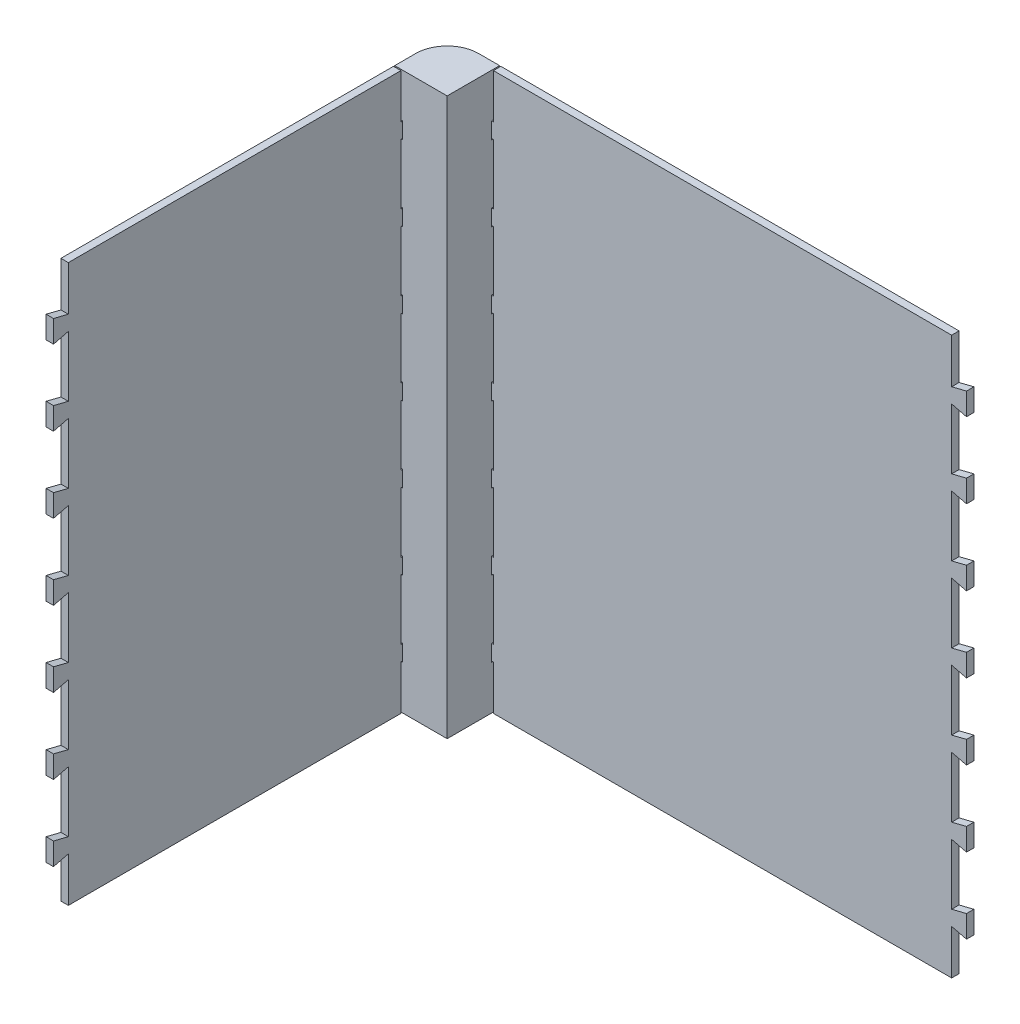
SolidWorks part; units mm, degrees
ref_plane "Front Plane" through (0, 0, 0) normal (0, 0, 1) x (1, 0, 0)
ref_plane "Top Plane" through (0, 0, 0) normal (0, 1, 0) x (1, 0, 0)
ref_plane "Right Plane" through (0, 0, 0) normal (1, 0, 0) x (0, 0, -1)
sketch "Constraints long side" plane through (0, 0, 0) normal (0, 0, 1) x (1, 0, 0)
  line L0 (-101.6, 112.5) -> (-101.6, -112.5) construction
  line L1 (-114.3, 112.5) -> (114.3, 112.5) construction
  line L2 (-114.3, 112.5) -> (-114.3, -112.5) construction
  line L3 (-114.3, -112.5) -> (114.3, -112.5) construction
  line L4 (114.3, 112.5) -> (114.3, -112.5) construction
  line L5 (101.6, 112.5) -> (101.6, -112.5) construction
  line L6 (-101.6, 0) -> (-114.3, 0) construction
  line L7 (114.3, 0) -> (101.6, 0) construction
  line L8 (-92.6, -112.5) -> (-92.6, 112.5) construction
  line L9 (92.6, -112.5) -> (92.6, 112.5) construction
  line L10 (-92.6, 0) -> (-101.6, 0) construction
  line L11 (101.6, 0) -> (92.6, 0) construction
  point P4 (0, 112.5)
  point P6 (-114.3, 0)
  point P20 (0, 0)
  dimension "D1" = 228.6
  dimension "D2" = 225
  dimension "D3" = 12.7
  dimension "D4" = 9
sketch "Constraints short side" plane through (0, 0, 0) normal (1, 0, 0) x (0, 0, -1)
  line L0 (0, 112.5) -> (0, -112.5) construction
  line L1 (0, 112.5) -> (0, -112.5) construction
  line L2 (-76.2, 112.5) -> (-76.2, -112.5) construction
  line L3 (-88.9, 112.5) -> (88.9, 112.5) construction
  line L4 (-88.9, 112.5) -> (-88.9, -112.5) construction
  line L5 (-88.9, -112.5) -> (88.9, -112.5) construction
  line L6 (88.9, 112.5) -> (88.9, -112.5) construction
  line L7 (76.2, 112.5) -> (76.2, -112.5) construction
  line L8 (-76.2, 0) -> (-88.9, 0) construction
  line L9 (76.2, 0) -> (88.9, 0) construction
  line L10 (-67.2, 112.5) -> (-67.2, -112.5) construction
  line L11 (-67.2, 0) -> (-76.2, 0) construction
  line L12 (67.2, 112.5) -> (67.2, -112.5) construction
  line L13 (76.2, 0) -> (67.2, 0) construction
  point P6 (0, 112.5)
  point P7 (0, -112.5)
  point P21 (0, 0)
  point P23 (0, 0)
  dimension "D1" = 177.8
  dimension "D2" = 12.7
  dimension "D3" = 9
sketch "Sketch3" plane through (0, 0, 0) normal (0, 0, 1) x (1, 0, 0)
  line L0 (-98.6, 4.5) -> (-98.6, -4.5)
  line L1 (-98.6, -4.5) -> (-92.6, -3)
  line L2 (-92.6, -112.5) -> (-92.6, 112.5) construction
  line L3 (-98.6, 4.5) -> (-92.6, 3)
  line L4 (-92.6, 3) -> (-92.6, -3)
  line L5 (-92.6, 0) -> (-101.6, 0) construction
  line L6 (-101.6, 112.5) -> (-101.6, -112.5) construction
  line L7 (-98.6, -25.98) -> (-92.6, -27.48)
  line L8 (-92.6, 112.5) -> (92.6, 112.5)
  line L9 (-92.6, 112.5) -> (-92.6, -112.5)
  line L10 (-92.6, -112.5) -> (92.6, -112.5)
  line L11 (92.6, 112.5) -> (92.6, -112.5)
  line L12 (-98.6, -25.98) -> (-98.6, -34.98)
  line L13 (-98.6, -34.98) -> (-92.6, -33.48)
  line L14 (-98.6, -56.46) -> (-92.6, -57.96)
  line L15 (-98.6, -56.46) -> (-98.6, -65.46)
  line L16 (-98.6, -65.46) -> (-92.6, -63.96)
  line L17 (-98.6, -86.94) -> (-92.6, -88.44)
  line L18 (-98.6, -86.94) -> (-98.6, -95.94)
  line L19 (-98.6, -95.94) -> (-92.6, -94.44)
  line L20 (-98.6, -30.48) -> (-92.6, -30.48) construction
  line L21 (-98.6, 0) -> (-92.6, 0) construction
  line L22 (-98.6, 95.94) -> (-92.6, 94.44)
  line L23 (-98.6, 86.94) -> (-92.6, 88.44)
  line L24 (-98.6, 86.94) -> (-98.6, 95.94)
  line L25 (-98.6, 65.46) -> (-92.6, 63.96)
  line L26 (-98.6, 56.46) -> (-98.6, 65.46)
  line L27 (-98.6, 56.46) -> (-92.6, 57.96)
  line L28 (-98.6, 25.98) -> (-92.6, 27.48)
  line L29 (-98.6, 25.98) -> (-98.6, 34.98)
  line L30 (-98.6, 34.98) -> (-92.6, 33.48)
  line L31 (0, 112.5) -> (0, -112.5) construction
  line L32 (98.6, 86.94) -> (92.6, 88.44)
  line L33 (98.6, 86.94) -> (98.6, 95.94)
  line L34 (98.6, 95.94) -> (92.6, 94.44)
  line L35 (98.6, 65.46) -> (92.6, 63.96)
  line L36 (98.6, 56.46) -> (98.6, 65.46)
  line L37 (98.6, 56.46) -> (92.6, 57.96)
  line L38 (98.6, 34.98) -> (92.6, 33.48)
  line L39 (98.6, 25.98) -> (98.6, 34.98)
  line L40 (98.6, 25.98) -> (92.6, 27.48)
  line L41 (98.6, -4.5) -> (92.6, -3)
  line L42 (98.6, 4.5) -> (98.6, -4.5)
  line L43 (98.6, 4.5) -> (92.6, 3)
  line L44 (98.6, -25.98) -> (92.6, -27.48)
  line L45 (98.6, -25.98) -> (98.6, -34.98)
  line L46 (98.6, -34.98) -> (92.6, -33.48)
  line L47 (98.6, -56.46) -> (92.6, -57.96)
  line L48 (98.6, -56.46) -> (98.6, -65.46)
  line L49 (98.6, -65.46) -> (92.6, -63.96)
  line L50 (98.6, -86.94) -> (92.6, -88.44)
  line L51 (98.6, -86.94) -> (98.6, -95.94)
  line L52 (98.6, -95.94) -> (92.6, -94.44)
  point P3 (-98.6, 0)
  point P9 (-92.6, 0)
  dimension "D1" = 6
  dimension "D2" = 9
  dimension "D3" = 3
  dimension "D5" = 30.48
  dimension "D4" = 4
sketch "Sketch4" plane through (0, 0, 0) normal (1, 0, 0) x (0, 0, -1)
  line L0 (-67.2, 3) -> (-73.2, 4.5)
  line L1 (-67.2, 112.5) -> (67.2, 112.5)
  line L2 (-67.2, 112.5) -> (-67.2, -112.5)
  line L3 (-67.2, -112.5) -> (67.2, -112.5)
  line L4 (67.2, 112.5) -> (67.2, -112.5)
  line L5 (-73.2, 4.5) -> (-73.2, -4.5)
  line L6 (-73.2, -4.5) -> (-67.2, -3)
  line L7 (-67.2, 0) -> (-76.2, 0) construction
  line L8 (-67.2, 3) -> (-67.2, -3) construction
  line L9 (-76.2, 112.5) -> (-76.2, -112.5) construction
  line L10 (-73.2, -34.98) -> (-67.2, -33.48)
  line L11 (-73.2, -25.98) -> (-73.2, -34.98)
  line L12 (-67.2, -27.48) -> (-73.2, -25.98)
  line L13 (-73.2, -65.46) -> (-67.2, -63.96)
  line L14 (-73.2, -56.46) -> (-73.2, -65.46)
  line L15 (-67.2, -57.96) -> (-73.2, -56.46)
  line L16 (-73.2, -95.94) -> (-67.2, -94.44)
  line L17 (-73.2, -86.94) -> (-73.2, -95.94)
  line L18 (-67.2, -88.44) -> (-73.2, -86.94)
  line L19 (-73.2, -30.48) -> (-67.2, -30.48) construction
  line L20 (-73.2, 0) -> (-67.2, 0) construction
  line L21 (-73.2, 95.94) -> (-67.2, 94.44)
  line L22 (-73.2, 86.94) -> (-73.2, 95.94)
  line L23 (-67.2, 88.44) -> (-73.2, 86.94)
  line L24 (-73.2, 65.46) -> (-67.2, 63.96)
  line L25 (-73.2, 56.46) -> (-73.2, 65.46)
  line L26 (-67.2, 57.96) -> (-73.2, 56.46)
  line L27 (-73.2, 34.98) -> (-67.2, 33.48)
  line L28 (-73.2, 25.98) -> (-73.2, 34.98)
  line L29 (-67.2, 27.48) -> (-73.2, 25.98)
  line L30 (-73.2, 4.5) -> (-67.2, 3)
  line L31 (-67.2, -3) -> (-73.2, -4.5)
  line L32 (0, 112.5) -> (0, -112.5) construction
  line L33 (73.2, 0) -> (67.2, 0) construction
  line L34 (73.2, -30.48) -> (67.2, -30.48) construction
  line L35 (67.2, -3) -> (73.2, -4.5)
  line L36 (73.2, 4.5) -> (67.2, 3)
  line L37 (67.2, 27.48) -> (73.2, 25.98)
  line L38 (73.2, 25.98) -> (73.2, 34.98)
  line L39 (73.2, 34.98) -> (67.2, 33.48)
  line L40 (67.2, 57.96) -> (73.2, 56.46)
  line L41 (73.2, 56.46) -> (73.2, 65.46)
  line L42 (73.2, 65.46) -> (67.2, 63.96)
  line L43 (67.2, 88.44) -> (73.2, 86.94)
  line L44 (73.2, 86.94) -> (73.2, 95.94)
  line L45 (73.2, 95.94) -> (67.2, 94.44)
  line L46 (67.2, -88.44) -> (73.2, -86.94)
  line L47 (73.2, -86.94) -> (73.2, -95.94)
  line L48 (73.2, -95.94) -> (67.2, -94.44)
  line L49 (67.2, -57.96) -> (73.2, -56.46)
  line L50 (73.2, -56.46) -> (73.2, -65.46)
  line L51 (73.2, -65.46) -> (67.2, -63.96)
  line L52 (67.2, -27.48) -> (73.2, -25.98)
  line L53 (73.2, -25.98) -> (73.2, -34.98)
  line L54 (73.2, -34.98) -> (67.2, -33.48)
  line L55 (73.2, -4.5) -> (67.2, -3)
  line L56 (73.2, 4.5) -> (73.2, -4.5)
  line L57 (67.2, 3) -> (73.2, 4.5)
  point P8 (-73.2, 0)
  point P15 (-67.2, 0)
  point P16 (-67.2, 0)
  dimension "D1" = 9
  dimension "D2" = 6
  dimension "D3" = 3
  dimension "D5" = 30.48
  dimension "D4" = 4
ref_plane "Plane5" through (-114.3, 0, 0) normal (1, 0, 0) x (0, 0, -1)
sketch "Sketch6" plane through (-114.3, 0, 0) normal (1, 0, 0) x (0, 0, -1)
  line L0 (-73.2, 4.5) -> (-73.2, -4.5) construction
  line L1 (-73.2, -95.94) -> (-67.2, -94.44) construction
  line L2 (-73.2, -86.94) -> (-73.2, -95.94) construction
  line L3 (-67.2, -88.44) -> (-73.2, -86.94) construction
  line L4 (-73.2, -65.46) -> (-67.2, -63.96) construction
  line L5 (-73.2, -56.46) -> (-73.2, -65.46) construction
  line L6 (-67.2, -57.96) -> (-73.2, -56.46) construction
  line L7 (-73.2, -34.98) -> (-67.2, -33.48) construction
  line L8 (-73.2, -25.98) -> (-73.2, -34.98) construction
  line L9 (-67.2, -27.48) -> (-73.2, -25.98) construction
  line L10 (-73.2, 34.98) -> (-67.2, 33.48) construction
  line L11 (-73.2, 25.98) -> (-73.2, 34.98) construction
  line L12 (-67.2, 27.48) -> (-73.2, 25.98) construction
  line L13 (-73.2, 65.46) -> (-67.2, 63.96) construction
  line L14 (-73.2, 56.46) -> (-73.2, 65.46) construction
  line L15 (-67.2, 57.96) -> (-73.2, 56.46) construction
  line L16 (-73.2, 95.94) -> (-67.2, 94.44) construction
  line L17 (-73.2, 86.94) -> (-73.2, 95.94) construction
  line L18 (-67.2, 88.44) -> (-73.2, 86.94) construction
  line L19 (67.2, 57.96) -> (73.2, 56.46) construction
  line L20 (73.2, 56.46) -> (73.2, 65.46) construction
  line L21 (73.2, 65.46) -> (67.2, 63.96) construction
  line L22 (67.2, 27.48) -> (73.2, 25.98) construction
  line L23 (73.2, 25.98) -> (73.2, 34.98) construction
  line L24 (73.2, 34.98) -> (67.2, 33.48) construction
  line L25 (73.2, 4.5) -> (73.2, -4.5) construction
  line L26 (67.2, -27.48) -> (73.2, -25.98) construction
  line L27 (73.2, -25.98) -> (73.2, -34.98) construction
  line L28 (73.2, -34.98) -> (67.2, -33.48) construction
  line L29 (67.2, -57.96) -> (73.2, -56.46) construction
  line L30 (73.2, -56.46) -> (73.2, -65.46) construction
  line L31 (73.2, -65.46) -> (67.2, -63.96) construction
  line L32 (67.2, -88.44) -> (73.2, -86.94) construction
  line L33 (73.2, -86.94) -> (73.2, -95.94) construction
  line L34 (73.2, -95.94) -> (67.2, -94.44) construction
  line L35 (67.2, 88.44) -> (73.2, 86.94) construction
  line L36 (73.2, 86.94) -> (73.2, 95.94) construction
  line L37 (73.2, 95.94) -> (67.2, 94.44) construction
  line L38 (-73.2, -4.5) -> (-67.2, -3) construction
  line L39 (-67.2, -3) -> (-73.2, -4.5) construction
  line L40 (-67.2, 112.5) -> (67.2, 112.5) construction
  line L41 (67.2, 112.5) -> (67.2, -112.5) construction
  line L42 (-67.2, -112.5) -> (67.2, -112.5) construction
  line L43 (-67.2, 112.5) -> (-67.2, -112.5) construction
  line L44 (-67.2, 3) -> (-73.2, 4.5) construction
  line L45 (-73.2, 4.5) -> (-67.2, 3) construction
  line L46 (73.2, 4.5) -> (67.2, 3) construction
  line L47 (67.2, 3) -> (73.2, 4.5) construction
  line L48 (67.2, -3) -> (73.2, -4.5) construction
  line L49 (73.2, -4.5) -> (67.2, -3) construction
  line L50 (-73.2, 4.5) -> (-73.2, -4.5)
  line L51 (-73.2, -95.94) -> (-67.2, -94.44)
  line L52 (-73.2, -86.94) -> (-73.2, -95.94)
  line L53 (-67.2, -88.44) -> (-73.2, -86.94)
  line L54 (-73.2, -65.46) -> (-67.2, -63.96)
  line L55 (-73.2, -56.46) -> (-73.2, -65.46)
  line L56 (-67.2, -57.96) -> (-73.2, -56.46)
  line L57 (-73.2, -34.98) -> (-67.2, -33.48)
  line L58 (-73.2, -25.98) -> (-73.2, -34.98)
  line L59 (-67.2, -27.48) -> (-73.2, -25.98)
  line L60 (-73.2, 34.98) -> (-67.2, 33.48)
  line L61 (-73.2, 25.98) -> (-73.2, 34.98)
  line L62 (-67.2, 27.48) -> (-73.2, 25.98)
  line L63 (-73.2, 65.46) -> (-67.2, 63.96)
  line L64 (-73.2, 56.46) -> (-73.2, 65.46)
  line L65 (-67.2, 57.96) -> (-73.2, 56.46)
  line L66 (-73.2, 95.94) -> (-67.2, 94.44)
  line L67 (-73.2, 86.94) -> (-73.2, 95.94)
  line L68 (-67.2, 88.44) -> (-73.2, 86.94)
  line L69 (67.2, 57.96) -> (73.2, 56.46)
  line L70 (73.2, 56.46) -> (73.2, 65.46)
  line L71 (73.2, 65.46) -> (67.2, 63.96)
  line L72 (67.2, 27.48) -> (73.2, 25.98)
  line L73 (73.2, 25.98) -> (73.2, 34.98)
  line L74 (73.2, 34.98) -> (67.2, 33.48)
  line L75 (73.2, 4.5) -> (73.2, -4.5)
  line L76 (67.2, -27.48) -> (73.2, -25.98)
  line L77 (73.2, -25.98) -> (73.2, -34.98)
  line L78 (73.2, -34.98) -> (67.2, -33.48)
  line L79 (67.2, -57.96) -> (73.2, -56.46)
  line L80 (73.2, -56.46) -> (73.2, -65.46)
  line L81 (73.2, -65.46) -> (67.2, -63.96)
  line L82 (67.2, -88.44) -> (73.2, -86.94)
  line L83 (73.2, -86.94) -> (73.2, -95.94)
  line L84 (73.2, -95.94) -> (67.2, -94.44)
  line L85 (67.2, 88.44) -> (73.2, 86.94)
  line L86 (73.2, 86.94) -> (73.2, 95.94)
  line L87 (73.2, 95.94) -> (67.2, 94.44)
  line L88 (-73.2, -4.5) -> (-67.2, -3)
  line L89 (-67.2, -3) -> (-73.2, -4.5)
  line L90 (-67.2, 112.5) -> (67.2, 112.5)
  line L91 (67.2, 112.5) -> (67.2, -112.5)
  line L92 (-67.2, -112.5) -> (67.2, -112.5)
  line L93 (-67.2, 112.5) -> (-67.2, -112.5)
  line L94 (-67.2, 3) -> (-73.2, 4.5)
  line L95 (-73.2, 4.5) -> (-67.2, 3)
  line L96 (73.2, 4.5) -> (67.2, 3)
  line L97 (67.2, 3) -> (73.2, 4.5)
  line L98 (67.2, -3) -> (73.2, -4.5)
  line L99 (73.2, -4.5) -> (67.2, -3)
extrude "Boss-Extrude1" add sketch "Sketch6" along normal blind 3 contours L82 L91 L84 L83 | L79 L91 L81 L80 | L76 L91 L78 L77 | L90 L93 L92 L91 | L91 L98 L75 L96 | L74 L91 L72 L73 | L71 L91 L69 L70 | L87 L91 L85 L86 | L93 L53 L52 L51 | L93 L56 L55 L54 | L93 L59 L58 L57 | L93 L94 L50 L88 | L93 L60 L61 L62 | L93 L63 L64 L65 | L93 L66 L67 L68 region at (-114.3, 0, 70.4) region at (-114.3, 0, 0) region at (-114.3, 30.48, 70.4) region at (-114.3, -30.48, 70.4) region at (-114.3, 60.96, 70.4) region at (-114.3, -60.96, 70.4) region at (-114.3, 91.44, 70.4) region at (-114.3, -91.44, 70.4) region at (-114.3, 91.44, -70.4) region at (-114.3, -91.44, -70.4) region at (-114.3, 60.96, -70.4) region at (-114.3, -60.96, -70.4) region at (-114.3, 30.48, -70.4) region at (-114.3, -30.48, -70.4) region at (-114.3, 0, -70.4)
ref_plane "Plane6" through (0, 0, -88.9) normal (0, 0, 1) x (1, 0, 0)
sketch "Sketch7" plane through (0, 0, -88.9) normal (0, 0, 1) x (1, 0, 0)
  line L0 (-98.6, -86.94) -> (-92.6, -88.44) construction
  line L1 (-98.6, -86.94) -> (-98.6, -95.94) construction
  line L2 (-98.6, -95.94) -> (-92.6, -94.44) construction
  line L3 (-98.6, -56.46) -> (-92.6, -57.96) construction
  line L4 (92.6, 112.5) -> (-92.6, 112.5)
  line L5 (92.6, -112.5) -> (92.6, 112.5)
  line L6 (-92.6, -112.5) -> (92.6, -112.5)
  line L7 (-92.6, 112.5) -> (-92.6, -112.5)
  line L8 (92.6, 112.5) -> (-92.6, 112.5)
  line L9 (92.6, -112.5) -> (92.6, 112.5)
  line L10 (-92.6, -112.5) -> (92.6, -112.5)
  line L11 (-92.6, 112.5) -> (-92.6, -112.5)
  line L12 (-98.6, 4.5) -> (-98.6, -4.5)
  line L13 (-98.6, -4.5) -> (-92.6, -3)
  line L14 (-92.6, -3) -> (-92.6, 3)
  line L15 (-92.6, 3) -> (-98.6, 4.5)
  line L16 (-98.6, 4.5) -> (-98.6, -4.5)
  line L17 (-98.6, -4.5) -> (-92.6, -3)
  line L18 (-92.6, -3) -> (-92.6, 3)
  line L19 (-92.6, 3) -> (-98.6, 4.5)
  line L20 (-98.6, -56.46) -> (-98.6, -65.46) construction
  line L21 (-98.6, -65.46) -> (-92.6, -63.96) construction
  line L22 (-98.6, -25.98) -> (-92.6, -27.48) construction
  line L23 (-98.6, -25.98) -> (-98.6, -34.98) construction
  line L24 (-98.6, -34.98) -> (-92.6, -33.48) construction
  line L25 (-98.6, 25.98) -> (-92.6, 27.48) construction
  line L26 (-98.6, 25.98) -> (-98.6, 34.98) construction
  line L27 (-98.6, 34.98) -> (-92.6, 33.48) construction
  line L28 (-98.6, 65.46) -> (-92.6, 63.96) construction
  line L29 (-98.6, 56.46) -> (-98.6, 65.46) construction
  line L30 (-98.6, 56.46) -> (-92.6, 57.96) construction
  line L31 (-98.6, 95.94) -> (-92.6, 94.44) construction
  line L32 (-98.6, 86.94) -> (-98.6, 95.94) construction
  line L33 (-98.6, 86.94) -> (-92.6, 88.44) construction
  line L34 (98.6, -4.5) -> (92.6, -3) construction
  line L35 (98.6, 4.5) -> (98.6, -4.5) construction
  line L36 (98.6, 4.5) -> (92.6, 3) construction
  line L37 (98.6, 34.98) -> (92.6, 33.48) construction
  line L38 (98.6, 25.98) -> (98.6, 34.98) construction
  line L39 (98.6, 25.98) -> (92.6, 27.48) construction
  line L40 (98.6, 65.46) -> (92.6, 63.96) construction
  line L41 (98.6, 56.46) -> (98.6, 65.46) construction
  line L42 (98.6, 56.46) -> (92.6, 57.96) construction
  line L43 (98.6, 86.94) -> (92.6, 88.44) construction
  line L44 (98.6, 86.94) -> (98.6, 95.94) construction
  line L45 (98.6, 95.94) -> (92.6, 94.44) construction
  line L46 (98.6, -86.94) -> (92.6, -88.44) construction
  line L47 (98.6, -86.94) -> (98.6, -95.94) construction
  line L48 (98.6, -95.94) -> (92.6, -94.44) construction
  line L49 (98.6, -56.46) -> (92.6, -57.96) construction
  line L50 (98.6, -56.46) -> (98.6, -65.46) construction
  line L51 (98.6, -65.46) -> (92.6, -63.96) construction
  line L52 (98.6, -25.98) -> (92.6, -27.48) construction
  line L53 (98.6, -25.98) -> (98.6, -34.98) construction
  line L54 (98.6, -34.98) -> (92.6, -33.48) construction
  line L55 (-98.6, -86.94) -> (-92.6, -88.44)
  line L56 (-98.6, -86.94) -> (-98.6, -95.94)
  line L57 (-98.6, -95.94) -> (-92.6, -94.44)
  line L58 (-98.6, -56.46) -> (-92.6, -57.96)
  line L59 (-98.6, -56.46) -> (-98.6, -65.46)
  line L60 (-98.6, -65.46) -> (-92.6, -63.96)
  line L61 (-98.6, -25.98) -> (-92.6, -27.48)
  line L62 (-98.6, -25.98) -> (-98.6, -34.98)
  line L63 (-98.6, -34.98) -> (-92.6, -33.48)
  line L64 (-98.6, 25.98) -> (-92.6, 27.48)
  line L65 (-98.6, 25.98) -> (-98.6, 34.98)
  line L66 (-98.6, 34.98) -> (-92.6, 33.48)
  line L67 (-98.6, 65.46) -> (-92.6, 63.96)
  line L68 (-98.6, 56.46) -> (-98.6, 65.46)
  line L69 (-98.6, 56.46) -> (-92.6, 57.96)
  line L70 (-98.6, 95.94) -> (-92.6, 94.44)
  line L71 (-98.6, 86.94) -> (-98.6, 95.94)
  line L72 (-98.6, 86.94) -> (-92.6, 88.44)
  line L73 (98.6, -4.5) -> (92.6, -3)
  line L74 (98.6, 4.5) -> (98.6, -4.5)
  line L75 (98.6, 4.5) -> (92.6, 3)
  line L76 (98.6, 34.98) -> (92.6, 33.48)
  line L77 (98.6, 25.98) -> (98.6, 34.98)
  line L78 (98.6, 25.98) -> (92.6, 27.48)
  line L79 (98.6, 65.46) -> (92.6, 63.96)
  line L80 (98.6, 56.46) -> (98.6, 65.46)
  line L81 (98.6, 56.46) -> (92.6, 57.96)
  line L82 (98.6, 86.94) -> (92.6, 88.44)
  line L83 (98.6, 86.94) -> (98.6, 95.94)
  line L84 (98.6, 95.94) -> (92.6, 94.44)
  line L85 (98.6, -86.94) -> (92.6, -88.44)
  line L86 (98.6, -86.94) -> (98.6, -95.94)
  line L87 (98.6, -95.94) -> (92.6, -94.44)
  line L88 (98.6, -56.46) -> (92.6, -57.96)
  line L89 (98.6, -56.46) -> (98.6, -65.46)
  line L90 (98.6, -65.46) -> (92.6, -63.96)
  line L91 (98.6, -25.98) -> (92.6, -27.48)
  line L92 (98.6, -25.98) -> (98.6, -34.98)
  line L93 (98.6, -34.98) -> (92.6, -33.48)
  dimension "D1" = 0
  dimension "D2" = 0
extrude "Boss-Extrude2" add sketch "Sketch7" along normal blind 3 separate body contours L8 L11 L10 L9 | L87 L86 L85 L9 | L90 L89 L88 L9 | L93 L92 L91 L9 | L74 L75 L9 L73 | L78 L77 L76 L9 | L81 L80 L79 L9 | L83 L84 L9 L82 | L56 L57 L11 L55 | L59 L60 L11 L58 | L62 L63 L11 L61 | L11 L19 L16 L17 | L66 L65 L64 L11 | L68 L69 L11 L67 | L71 L72 L11 L70 region at (0, 0, -88.9) region at (95.8, 91.44, -88.9) region at (-95.8, 91.44, -88.9) region at (95.8, 60.96, -88.9) region at (-95.8, 60.96, -88.9) region at (95.8, 30.48, -88.9) region at (-95.8, 30.48, -88.9) region at (95.8, 0, -88.9) region at (-95.8, 0, -88.9) region at (95.8, -30.48, -88.9) region at (-95.8, -30.48, -88.9) region at (95.8, -60.96, -88.9) region at (-95.8, -60.96, -88.9) region at (95.8, -91.44, -88.9) region at (-95.8, -91.44, -88.9)
sketch "Sketch8" plane through (0, 0, 0) normal (0, 1, 0) x (1, 0, 0)
  line L0 (-101.6, 0) -> (-101.6, 88.9) construction
  line L2 (-92.6, 0) -> (-101.6, 0) construction
  line L3 (-123.75, 88.9) -> (123.75, 88.9) construction
  line L4 (0, 76.2) -> (0, 88.9) construction
  line L5 (0, 76.2) -> (0, 88.9)
  line L6 (0, 76.2) -> (-114.3, 76.2) construction
  line L7 (-114.3, -97.79) -> (-114.3, 97.79) construction
  line L8 (-114.3, 76.2) -> (-114.3, 67.7)
  line L9 (0, 76.2) -> (0, 67.2) construction
  line L10 (0, 76.2) -> (0, 67.2)
  line L11 (-92.6, 0) -> (-101.6, 0)
  line L12 (-101.6, 88.9) -> (-93.1, 88.9)
  line L13 (-114.3, 67.7) -> (-93.1, 67.7)
  line L14 (-93.1, 67.7) -> (-93.1, 88.9)
  arc A0 (-114.3, 76.2) -> (-101.6, 88.9) centre (-101.6, 76.2) cw
  point P9 (-101.6, 0)
  point P11 (-101.6, 76.2)
  dimension "D1" = 0.5
  dimension "D2" = 0.5
sketch "Sketch9" plane through (0, 0, 0) normal (0, 1, 0) x (1, 0, 0)
  line L4 (-114.3, 67.7) -> (-93.1, 67.7)
  line L5 (-93.1, 67.7) -> (-93.1, 88.9)
  line L6 (-93.1, 88.9) -> (-101.6, 88.9)
  line L7 (-114.3, 76.2) -> (-114.3, 67.7)
  line L8 (-114.3, 67.7) -> (-93.1, 67.7)
  line L9 (-93.1, 67.7) -> (-93.1, 88.9)
  line L10 (-93.1, 88.9) -> (-101.6, 88.9)
  line L11 (-114.3, 76.2) -> (-114.3, 67.7)
  arc A1 (-101.6, 88.9) -> (-114.3, 76.2) centre (-101.6, 76.2) ccw
  arc A2 (-101.6, 88.9) -> (-114.3, 76.2) centre (-101.6, 76.2) ccw
  dimension "D1" = 0
extrude "Boss-Extrude3" add sketch "Sketch9" along normal up to vertex (112.5 mm away) and the other way up to vertex (112.5 mm away) separate body up to point (0, 112.5, -76.2) other way up to point (0, -112.5, -76.2)
sketch "Sketch10" plane through (0, 0, -88.9) normal (0, 0, 1) x (1, 0, 0)
  line L0 (-98.8, 65.7162) -> (-92.5515, 64.154)
  line L3 (-98.8, 56.2038) -> (-98.8, 65.7162)
  line L23 (-98.8, 56.2038) -> (-92.5515, 57.766)
  line L25 (-98.8, 35.2362) -> (-92.5515, 33.674)
  line L28 (-98.8, 25.7238) -> (-98.8, 35.2362)
  line L31 (-98.6, 95.94) -> (-92.6, 94.44) construction
  line L32 (-98.6, 86.94) -> (-98.6, 95.94) construction
  line L33 (-98.6, 86.94) -> (-92.6, 88.44) construction
  line L34 (-98.8, 25.7238) -> (-92.5515, 27.286)
  line L37 (-98.8, 4.7562) -> (-92.5515, 3.194)
  line L40 (-98.8, -4.7562) -> (-98.8, 4.7562)
  line L43 (-98.8, -4.7562) -> (-92.5515, -3.194)
  line L46 (-98.8, -25.7238) -> (-92.5515, -27.286)
  line L49 (-98.8, -35.2362) -> (-98.8, -25.7238)
  line L52 (-98.8, -35.2362) -> (-92.5515, -33.674)
  line L55 (-98.8, -56.2038) -> (-92.5515, -57.766)
  line L58 (-98.8, -65.7162) -> (-98.8, -56.2038)
  line L62 (-98.8, -65.7162) -> (-92.5515, -64.154)
  line L64 (-98.8, -86.6838) -> (-92.5515, -88.246)
  line L67 (-98.8, -96.1962) -> (-98.8, -86.6838)
  line L70 (-98.6, 95.94) -> (-92.6, 94.44)
  line L71 (-98.6, 86.94) -> (-98.6, 95.94)
  line L72 (-98.6, 86.94) -> (-92.6, 88.44)
  line L73 (-98.8, -96.1962) -> (-92.5515, -94.634)
  line L76 (-98.6, 56.46) -> (-98.6, 65.46) construction
  line L79 (-98.6, 56.46) -> (-98.6, 65.46)
  line L82 (-98.6, 60.96) -> (-92.6, 60.96) construction
  line L85 (-92.6, -112.5) -> (-92.6, 112.5) construction
  line L88 (-92.5515, -94.634) -> (-92.5515, -88.246)
  line L91 (-92.5515, -64.154) -> (-92.5515, -57.766)
  line L94 (-98.8, 86.6838) -> (-92.5515, 88.246)
  line L95 (-98.8, 86.6838) -> (-98.8, 96.1962)
  line L96 (-98.8, 96.1962) -> (-92.5515, 94.634)
  line L97 (-92.5515, -33.674) -> (-92.5515, -27.286)
  line L98 (-92.5515, -3.194) -> (-92.5515, 3.194)
  line L99 (-92.5515, 27.286) -> (-92.5515, 33.674)
  line L100 (-92.5515, 57.766) -> (-92.5515, 64.154)
  line L101 (-92.5515, 88.246) -> (-92.5515, 94.634)
  point P34 (-98.8, 60.96)
  dimension "D1" = 7
  dimension "D3" = 0.2
extrude "Cut-Extrude1" cut sketch "Sketch10" along normal blind 3.2 contours L67 L64 L88 L73 | L58 L55 L91 L62 | L49 L46 L97 L52 | L40 L37 L98 L43 | L28 L25 L99 L34 | L3 L0 L100 L23 | L95 L96 L101 L94
sketch "Sketch11" plane through (-114.3, 0, 0) normal (1, 0, 0) x (0, 0, -1)
  line L0 (73.4, 86.6838) -> (73.4, 96.1962)
  line L1 (73.4, 96.1962) -> (67, 94.5962)
  line L2 (67, 94.5962) -> (67, 88.2838)
  line L3 (67, 88.2838) -> (73.4, 86.6838)
  line L4 (67, 57.8038) -> (73.4, 56.2038)
  line L5 (73.4, 56.2038) -> (73.4, 65.7162)
  line L6 (73.4, 65.7162) -> (67, 64.1162)
  line L7 (67, 64.1162) -> (67, 57.8038)
  line L8 (67, 27.3238) -> (73.4, 25.7238)
  line L9 (73.4, 25.7238) -> (73.4, 35.2362)
  line L10 (73.4, 35.2362) -> (67, 33.6362)
  line L11 (67, 33.6362) -> (67, 27.3238)
  line L12 (67, -3.1562) -> (73.4, -4.7562)
  line L13 (73.4, -4.7562) -> (73.4, 4.7562)
  line L15 (73.4, 4.7562) -> (67, 3.1562)
  line L16 (67, 3.1562) -> (67, -3.1562)
  line L18 (67, -33.6362) -> (73.4, -35.2362)
  line L35 (67.2, 88.44) -> (73.2, 86.94) construction
  line L36 (73.2, 86.94) -> (73.2, 95.94) construction
  line L37 (73.2, 95.94) -> (67.2, 94.44) construction
  line L38 (73.4, -35.2362) -> (73.4, -25.7238)
  line L39 (73.4, -25.7238) -> (67, -27.3238)
  line L40 (67, -27.3238) -> (67, -33.6362)
  line L41 (67.2, 112.5) -> (67.2, -112.5) construction
  line L42 (67, -64.1162) -> (73.4, -65.7162)
  line L43 (73.4, -65.7162) -> (73.4, -56.2038)
  line L44 (73.4, -56.2038) -> (67, -57.8038)
  line L45 (67, -57.8038) -> (67, -64.1162)
  line L50 (67, -94.5962) -> (73.4, -96.1962)
  line L51 (73.4, -96.1962) -> (73.4, -86.6838)
  line L52 (73.4, -86.6838) -> (67, -88.2838)
  line L53 (67, -88.2838) -> (67, -94.5962)
  line L54 (73.2, 56.46) -> (73.2, 65.46) construction
  line L85 (67.2, 88.44) -> (73.2, 86.94) construction
  line L86 (73.2, 86.94) -> (73.2, 95.94) construction
  line L87 (73.2, 95.94) -> (67.2, 94.44) construction
  line L91 (67.2, 94.44) -> (67.2, 88.44) construction
  point P30 (73.2, 60.96)
  point P31 (73.4, 60.96)
  dimension "D1" = 0.2
  dimension "D2" = 7
extrude "Cut-Extrude2" cut sketch "Sketch11" along normal blind 3.2
